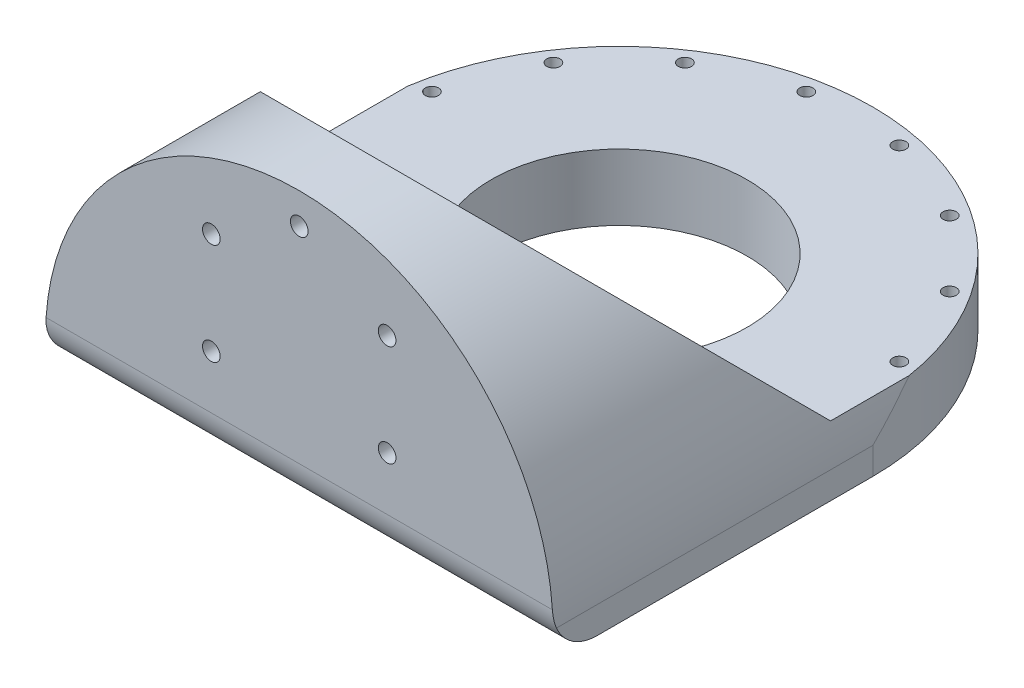
SolidWorks part; units mm, degrees
ref_plane "Front Plane" through (0, 0, 0) normal (0, 0, 1) x (1, 0, 0)
ref_plane "Top Plane" through (0, 0, 0) normal (0, 1, 0) x (1, 0, 0)
ref_plane "Right Plane" through (0, 0, 0) normal (1, 0, 0) x (0, 0, -1)
sketch "Sketch1" plane through (0, 0, 0) normal (0, 1, 0) x (1, 0, 0)
  line L0 (-10.5349, 52.9624) -> (0, 0) construction
  line L1 (0, 0) -> (0, 42.8379) construction
  line L2 (-57.5, 0) -> (-57.5, -57.5)
  line L3 (-57.5, -57.5) -> (57.5, -57.5)
  line L4 (57.5, -57.5) -> (57.5, 0)
  circle A0 centre (0, 0) radius 57.5
  circle A1 centre (0, 0) radius 29
  circle A2 centre (0, 0) radius 54 construction
  circle A3 centre (-10.5349, 52.9624) radius 1.5
  circle A4 centre (10.5349, 52.9624) radius 1.5
  circle A5 centre (30.0008, 44.8994) radius 1.5
  circle A6 centre (44.8994, 30.0008) radius 1.5
  circle A7 centre (52.9624, 10.5349) radius 1.5
  circle A8 centre (52.9624, -10.5349) radius 1.5
  circle A9 centre (44.8994, -30.0008) radius 1.5
  circle A10 centre (30.0008, -44.8994) radius 1.5
  circle A11 centre (10.5349, -52.9624) radius 1.5
  circle A12 centre (-10.5349, -52.9624) radius 1.5
  circle A13 centre (-30.0008, -44.8994) radius 1.5
  circle A14 centre (-44.8994, -30.0008) radius 1.5
  circle A15 centre (-52.9624, -10.5349) radius 1.5
  circle A16 centre (-52.9624, 10.5349) radius 1.5
  circle A17 centre (-44.8994, 30.0008) radius 1.5
  circle A18 centre (-30.0008, 44.8994) radius 1.5
  point P40 (0, 0)
  dimension "D1" = 115
  dimension "D2" = 58
  dimension "D3" = 108
  dimension "D4" = 3
  dimension "D5" = 11.25
  dimension "D6" = 16
extrude "Boss-Extrude1" add sketch "Sketch1" along normal blind 15 contours A0 A18 A17 A16 A15 A14 A13 A12 A11 A10 A9 A8 A7 A6 A5 A4 A3 A1 | A0 L2 L3 | A0 L3 L4 region at (-44.6563, 0, 44.6563) region at (0, 0, -55.8737) region at (44.6563, 0, 44.6563)
sketch "Sketch2" plane through (-57.5, 0, 0) normal (-1, 0, 0) x (0, 0, 1)
  line L0 (57.5, 0) -> (57.5, 63.6)
  line L1 (57.5, 63.6) -> (72.5, 63.6)
  line L2 (72.5, 63.6) -> (72.5, 0)
  line L3 (72.5, 0) -> (57.5, 0)
  line L4 (57.5, 63.6) -> (0, 15)
  line L5 (0, 15) -> (57.5, 15)
  line M6 (57.5, 0) -> (57.5, 15)
  line M7 (57.5, 15) -> (0, 15)
  dimension "D1" = 15
  dimension "D2" = 63.6
extrude "Boss-Extrude2" add sketch "Sketch2" against normal blind 115 contours L3 L2 L1 L0 M6 | L0 L4 M7 region at (-57.5, 31.8, 65) region at (-57.5, 31.2, 38.3333)
sketch "Sketch3" plane through (0, 63.6, 0) normal (0, 1, 0) x (1, 0, 0)
  circle A0 centre (0, 0) radius 57.5
extrude "Cut-Extrude1" cut sketch "Sketch3" against normal blind 48.6
sketch "Sketch5" plane through (0, 0, 72.5) normal (0, 0, 1) x (1, 0, 0)
  line L0 (0, 76.0834) -> (0, 0) construction
  line L1 (57.5, 63.6) -> (-57.5, 63.6) construction
  circle A0 centre (0, 33.6) radius 23 construction
  circle A1 centre (0, 33.6) radius 30 construction
  circle A2 centre (0, 56.6) radius 2
  circle A3 centre (-19.9186, 45.1) radius 2
  circle A4 centre (-19.9186, 22.1) radius 2
  circle A6 centre (19.9186, 22.1) radius 2
  circle A7 centre (19.9186, 45.1) radius 2
  circle A8 centre (0, 10.6) radius 2 [skipped]
  point P22 (0, 33.6)
  dimension "D1" = 46
  dimension "D2" = 60
  dimension "D3" = 4
  dimension "D4" = 6
extrude "Cut-Extrude3" cut sketch "Sketch5" against normal blind 75.6
sketch "Sketch6" plane through (0, 0, 0) normal (0, 0, 1) x (1, 0, 0)
  line L0 (57.5, 63.6) -> (-57.5, 63.6) construction
  circle A0 centre (0, 33.6) radius 23 construction
  circle A1 centre (0, 33.6) radius 30 construction
  circle A2 centre (0, 56.6) radius 4.25
  circle A3 centre (19.9186, 45.1) radius 4.25
  circle A4 centre (19.9186, 22.1) radius 4.25
  circle A6 centre (-19.9186, 22.1) radius 4.25
  circle A7 centre (-19.9186, 45.1) radius 4.25
  circle A8 centre (0, 10.6) radius 4.25 [skipped]
  point P19 (0, 33.6)
  dimension "D1" = 46
  dimension "D2" = 60
  dimension "D3" = 8.5
  dimension "D4" = 6
extrude "Cut-Extrude4" cut sketch "Sketch6" along normal blind 62.5
sketch "Sketch4" plane through (0, 0, 72.5) normal (0, 0, 1) x (1, 0, 0)
  line L0 (0, 71.5981) -> (0, -19.7592) construction
  line L1 (57.5, 63.6) -> (-57.5, 63.6) construction
  line L2 (-57.5, 0) -> (-57.5, 63.6)
  line L3 (-57.5, 63.6) -> (0, 63.6)
  line L4 (0, 63.6) -> (57.5, 63.6)
  line L5 (57.5, 63.6) -> (57.5, 0)
  circle A0 centre (0, 6.1) radius 57.5
  line M2 (-57.5, 63.6) -> (-57.5, 0)
  line M5 (57.5, 63.6) -> (-57.5, 63.6)
  dimension "D1" = 115
extrude "Cut-Extrude2" cut sketch "Sketch4" against normal blind 132.6 contours A0 M5 M2 | A0 L5 M5 region at (-44.6563, 50.7563, 72.5) region at (44.6563, 50.7563, 72.5)
fillet "Fillet1" radius 10 1 edges at (0, 0, 72.5)
